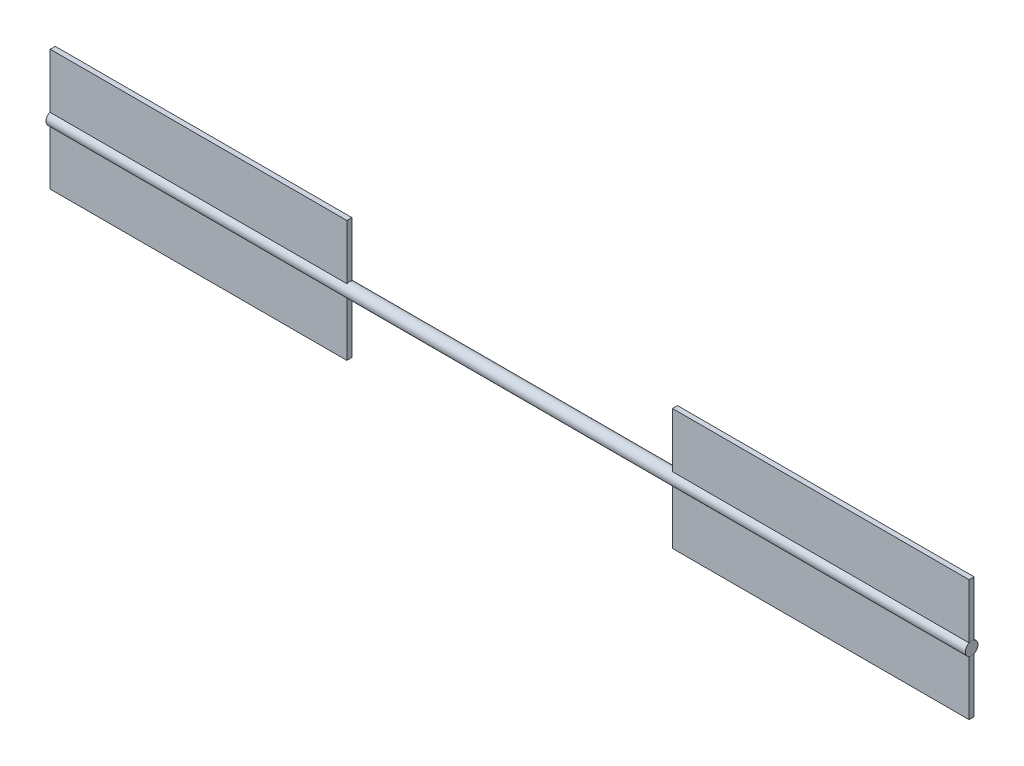
SolidWorks part; units mm, degrees
ref_plane "Front Plane" through (0, 0, 0) normal (0, 0, 1) x (1, 0, 0)
ref_plane "Top Plane" through (0, 0, 0) normal (0, 1, 0) x (1, 0, 0)
ref_plane "Right Plane" through (0, 0, 0) normal (1, 0, 0) x (0, 0, -1)
ref_plane "Plane1" through (0, 0, 197.8) normal (0, 0, -1) x (-1, 0, 0)
ref_plane "Plane2" through (2459.5297, 0, 0) normal (1, 0, 0) x (0, 0, -1)
ref_plane "Plane3" through (-1200.4703, 0, 0) normal (1, 0, 0) x (0, 0, -1)
sketch "Sketch6" plane through (2459.5297, 0, 0) normal (1, 0, 0) x (0, 0, -1)
  line L0 (-555.5, 0) -> (555.5, 0) construction
  line L1 (-197.8, -1179.3879) -> (-197.8, 1179.3879) construction
  circle A0 centre (-197.8, 0) radius 25.4
extrude "Boss-Extrude1" add sketch "Sketch6" against normal blind 3660
sketch "Sketch7" plane through (0, 0, 197.8) normal (0, 0, -1) x (-1, 0, 0)
  line L0 (-1278.362, 241.3) -> (-2459.462, 241.3)
  line L1 (-1278.362, 241.3) -> (-1278.362, -241.3)
  line L2 (-2459.462, 241.3) -> (-2459.462, -241.3)
  line L3 (-1278.362, -241.3) -> (-2459.462, -241.3)
  line L4 (-1278.362, 241.3) -> (-2459.462, -241.3) construction
  line L5 (-2459.462, 241.3) -> (-1278.362, -241.3) construction
  line L6 (-555.5, 0) -> (555.5, 0) construction
  line L7 (17.8955, -241.3) -> (1198.9955, -241.3)
  line L8 (17.8955, -241.3) -> (17.8955, 241.3)
  line L9 (1198.9955, -241.3) -> (1198.9955, 241.3)
  line L10 (17.8955, 241.3) -> (1198.9955, 241.3)
  line L11 (17.8955, -241.3) -> (1198.9955, 241.3) construction
  line L12 (1198.9955, -241.3) -> (17.8955, 241.3) construction
  point P0 (651.9593, 0)
  point P1 (-1868.912, 0)
  point P8 (608.4455, 0)
extrude "Boss-Extrude3" add sketch "Sketch7" along normal blind 10 and the other way blind 10
